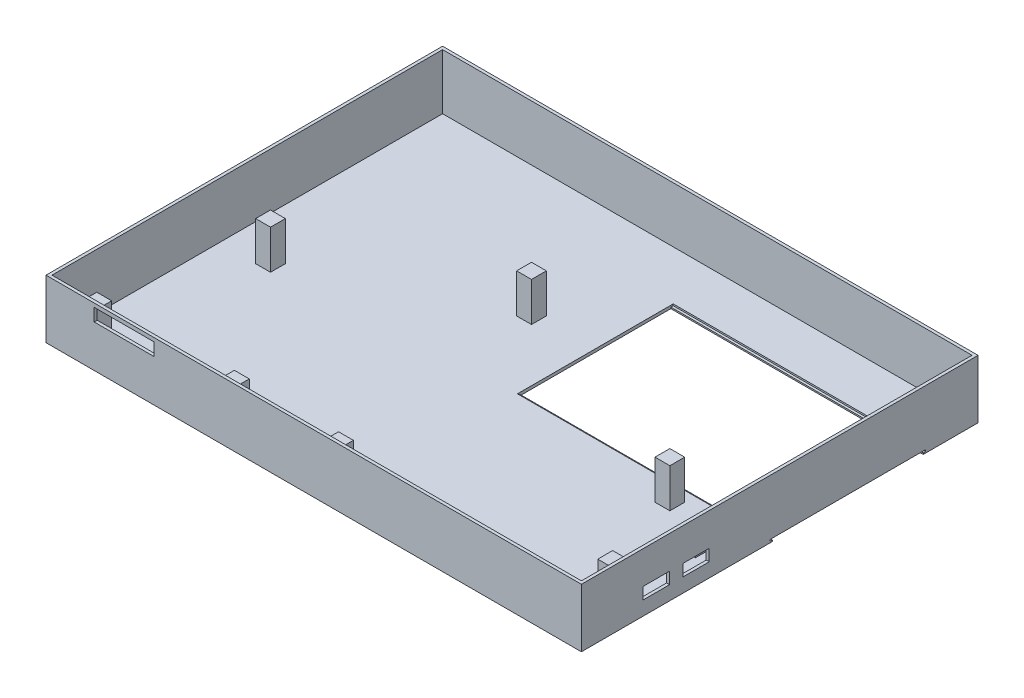
SolidWorks part; units mm, degrees
material "PLA"
ref_plane "Спереди" through (0, 0, 0) normal (0, 0, 1) x (1, 0, 0)
ref_plane "Сверху" through (0, 0, 0) normal (0, 1, 0) x (1, 0, 0)
ref_plane "Справа" through (0, 0, 0) normal (1, 0, 0) x (0, 0, -1)
sketch "Эскиз1" plane through (0, 0, 0) normal (0, 1, 0) x (1, 0, 0)
  line L1 (135, 100) -> (-135, 100)
  line L2 (135, 100) -> (135, -100)
  line L3 (135, -100) -> (-135, -100)
  line L4 (-135, 100) -> (-135, -100)
  line L5 (135, 100) -> (-135, -100) construction
  line L6 (135, -100) -> (-135, 100) construction
  point P0 (0, 0)
  dimension "D1" = 200
  dimension "D2" = 270
extrude "Бобышка-Вытянуть1" add sketch "Эскиз1" along normal blind 1.5
sketch "Эскиз2" plane through (0, 1.5, 0) normal (0, 1, 0) x (1, 0, 0)
  line L0 (133.5, 98.5) -> (-133.5, 98.5)
  line L1 (-133.5, 98.5) -> (-133.5, -98.5)
  line L2 (-133.5, -98.5) -> (-110.7, -98.5)
  line L3 (133.5, -98.5) -> (133.5, 98.5)
  line L4 (-135, 100) -> (-135, -100)
  line L5 (-135, -100) -> (135, -100)
  line L6 (135, -100) -> (135, 100)
  line L7 (135, 100) -> (-135, 100)
  line L8 (-135, 100) -> (-135, -100)
  line L9 (-135, -100) -> (-110.7, -100)
  line L10 (135, -100) -> (135, 100)
  line L11 (135, 100) -> (-135, 100)
  line L12 (-110.7, -98.5) -> (-110.7, -100)
  line L14 (-80.5, -98.5) -> (-80.5, -100)
  line L16 (-80.5, -98.5) -> (133.5, -98.5)
  line L17 (-80.5, -100) -> (135, -100)
  line L18 (-133.5, -98.5) -> (133.5, -98.5) construction
  line L20 (-135, -100) -> (135, -100) construction
  dimension "D3" = 24.3
  dimension "D4" = 54.5
  dimension "D1" = 0
  dimension "D2" = 1.5
extrude "Бобышка-Вытянуть2" add sketch "Эскиз2" along normal offset from surface (28 mm away) 7 offset beyond the face yes
sketch "Эскиз3" plane through (0, 1.5, 0) normal (0, 1, 0) x (1, 0, 0)
  line L1 (-110.7, -98.5) -> (-80.5, -98.5)
  line L2 (-110.7, -98.5) -> (-110.7, -100)
  line L3 (-110.7, -100) -> (-80.5, -100)
  line L4 (-80.5, -98.5) -> (-80.5, -100)
extrude "Бобышка-Вытянуть3" add sketch "Эскиз3" along normal blind 19.7
sketch "Эскиз4" plane through (-110.7, 0, 0) normal (1, 0, 0) x (0, 0, -1)
  line L0 (-100, 29.5) -> (-100, 21.2) construction
  line L1 (-98.5, 29.5) -> (-100, 29.5)
  line L2 (-98.5, 29.5) -> (-98.5, 27.6)
  line L3 (-98.5, 27.6) -> (-100, 27.6)
  line L4 (-100, 29.5) -> (-100, 27.6)
  dimension "D1" = 1.9
extrude "Бобышка-Вытянуть4" add sketch "Эскиз4" along normal up to surface (30.2 mm away) up to face at (-80.5, 25.35, 99.25)
sketch "Эскиз5" plane through (135, 0, 0) normal (1, 0, 0) x (0, 0, -1)
  line L0 (-100, 29.5) -> (-100, 0) construction
  line L1 (-55.55, 13) -> (-68.85, 13)
  line L2 (-55.55, 13) -> (-55.55, 7.1)
  line L3 (-55.55, 7.1) -> (-68.85, 7.1)
  line L4 (-68.85, 13) -> (-68.85, 7.1)
  line L5 (-55.55, 13) -> (-68.85, 7.1) construction
  line L6 (-55.55, 7.1) -> (-68.85, 13) construction
  line L7 (-35.55, 13) -> (-48.85, 13)
  line L8 (-35.55, 13) -> (-35.55, 7.1)
  line L9 (-35.55, 7.1) -> (-48.85, 7.1)
  line L10 (-48.85, 13) -> (-48.85, 7.1)
  line L11 (-35.55, 13) -> (-48.85, 7.1) construction
  line L12 (-35.55, 7.1) -> (-48.85, 13) construction
  line L13 (-100, 0) -> (100, 0) construction
  point P0 (-62.2, 10.05)
  point P5 (-42.2, 10.05)
  dimension "D1" = 13.3
  dimension "D2" = 5.9
  dimension "D3" = 6.7
  dimension "D4" = 31.15
  dimension "D5" = 13
extrude "Вырез-Вытянуть1" cut sketch "Эскиз5" against normal up to surface (1.5 mm away) up to face at (133.5, 15.5, 0)
sketch "Эскиз10" plane through (0, 1.5, 0) normal (0, 1, 0) x (1, 0, 0)
  line L0 (133.5, -14.85) -> (133.5, -98.5) construction
  line L1 (124.175, -24.225) -> (116.675, -24.225)
  line L2 (124.175, -24.225) -> (124.175, -31.725)
  line L3 (124.175, -31.725) -> (116.675, -31.725)
  line L4 (116.675, -24.225) -> (116.675, -31.725)
  line L5 (124.175, -24.225) -> (116.675, -31.725) construction
  line L6 (124.175, -31.725) -> (116.675, -24.225) construction
  line L7 (114.55, -56.3) -> (107.05, -56.3)
  line L8 (114.55, -56.3) -> (114.55, -63.8)
  line L9 (114.55, -63.8) -> (107.05, -63.8)
  line L10 (107.05, -56.3) -> (107.05, -63.8)
  line L11 (114.55, -56.3) -> (107.05, -63.8) construction
  line L12 (114.55, -63.8) -> (107.05, -56.3) construction
  line L13 (115.175, -89.275) -> (107.675, -89.275)
  line L14 (115.175, -89.275) -> (115.175, -96.775)
  line L15 (115.175, -96.775) -> (107.675, -96.775)
  line L16 (107.675, -89.275) -> (107.675, -96.775)
  line L17 (115.175, -89.275) -> (107.675, -96.775) construction
  line L18 (115.175, -96.775) -> (107.675, -89.275) construction
  line L19 (133.5, -98.5) -> (-133.5, -98.5) construction
  point P0 (120.425, -27.975)
  point P5 (110.8, -60.05)
  point P10 (111.425, -93.025)
  dimension "D1" = 13.075
  dimension "D2" = 70.525
  dimension "D3" = 22.7
  dimension "D4" = 38.45
  dimension "D5" = 22.075
  dimension "D6" = 5.475
  dimension "D7" = 7.5
extrude "Бобышка-Вытянуть6" add sketch "Эскиз10" along normal blind 6.9
sketch "Эскиз11" plane through (0, 1.5, 0) normal (0, 1, 0) x (1, 0, 0)
  line L1 (-46.7446, -85.75) -> (-54.2446, -85.75)
  line L2 (-46.7446, -85.75) -> (-46.7446, -93.25)
  line L3 (-46.7446, -93.25) -> (-54.2446, -93.25)
  line L4 (-54.2446, -85.75) -> (-54.2446, -93.25)
  line L5 (-46.7446, -85.75) -> (-54.2446, -93.25) construction
  line L6 (-46.7446, -93.25) -> (-54.2446, -85.75) construction
  line L7 (-19.0224, 28.8491) -> (-26.5224, 28.8491)
  line L8 (-19.0224, 28.8491) -> (-19.0224, 36.3491)
  line L9 (-19.0224, 36.3491) -> (-26.5224, 36.3491)
  line L10 (-26.5224, 28.8491) -> (-26.5224, 36.3491)
  line L11 (-19.0224, 28.8491) -> (-26.5224, 36.3491) construction
  line L12 (-19.0224, 36.3491) -> (-26.5224, 28.8491) construction
  line L13 (-115.5446, -93.8424) -> (-123.0446, -93.8424)
  line L14 (-115.5446, -93.8424) -> (-115.5446, -86.3424)
  line L15 (-115.5446, -86.3424) -> (-123.0446, -86.3424)
  line L16 (-123.0446, -93.8424) -> (-123.0446, -86.3424)
  line L17 (-115.5446, -93.8424) -> (-123.0446, -86.3424) construction
  line L18 (-115.5446, -86.3424) -> (-123.0446, -93.8424) construction
  line L19 (-107.65, -14.1324) -> (-115.15, -14.1324)
  line L20 (-107.65, -14.1324) -> (-107.65, -6.6324)
  line L21 (-107.65, -6.6324) -> (-115.15, -6.6324)
  line L22 (-115.15, -14.1324) -> (-115.15, -6.6324)
  line L23 (-107.65, -14.1324) -> (-115.15, -6.6324) construction
  line L24 (-107.65, -6.6324) -> (-115.15, -14.1324) construction
  line L25 (97.2279, -17.6196) -> (89.7279, -17.6196)
  line L26 (97.2279, -17.6196) -> (97.2279, -10.1196)
  line L27 (97.2279, -10.1196) -> (89.7279, -10.1196)
  line L28 (89.7279, -17.6196) -> (89.7279, -10.1196)
  line L29 (97.2279, -17.6196) -> (89.7279, -10.1196) construction
  line L30 (97.2279, -10.1196) -> (89.7279, -17.6196) construction
  line L31 (94.0554, -99.0196) -> (86.5554, -99.0196)
  line L32 (94.0554, -99.0196) -> (94.0554, -91.5196)
  line L33 (94.0554, -91.5196) -> (86.5554, -91.5196)
  line L34 (86.5554, -99.0196) -> (86.5554, -91.5196)
  line L35 (94.0554, -99.0196) -> (86.5554, -91.5196) construction
  line L36 (94.0554, -91.5196) -> (86.5554, -99.0196) construction
  line L37 (6.3554, -93.8285) -> (-1.1446, -93.8285)
  line L38 (6.3554, -93.8285) -> (6.3554, -86.3285)
  line L39 (6.3554, -86.3285) -> (-1.1446, -86.3285)
  line L40 (-1.1446, -93.8285) -> (-1.1446, -86.3285)
  line L41 (6.3554, -93.8285) -> (-1.1446, -86.3285) construction
  line L42 (6.3554, -86.3285) -> (-1.1446, -93.8285) construction
  line L44 (-133.5, 98.5) -> (133.5, 98.5) construction
  line L45 (-133.5, -98.5) -> (-133.5, 98.5) construction
  line L47 (133.5, -98.5) -> (-133.5, -98.5) construction
  line L48 (133.5, 98.5) -> (133.5, -98.5) construction
  point P0 (-50.4946, -89.5)
  point P5 (-22.7724, 32.5991)
  point P10 (-119.2946, -90.0924)
  point P15 (-111.4, -10.3824)
  point P20 (93.4779, -13.8696)
  point P25 (90.3054, -95.2696)
  point P30 (2.6054, -90.0785)
  dimension "D1" = 7.5
  dimension "D2" = 65.9009
  dimension "D3" = 110.7276
  dimension "D4" = 108.8824
  dimension "D5" = 22.1
  dimension "D6" = 8.4076
  dimension "D7" = 14.2054
  dimension "D8" = 8.4215
  dimension "D9" = 130.8946
  dimension "D10" = 9
  dimension "D11" = 83.0054
  dimension "D12" = 3.2304
  dimension "D13" = 43.1946
  dimension "D14" = 84.6304
  dimension "D15" = 40.0221
extrude "Бобышка-Вытянуть7" add sketch "Эскиз11" along normal blind 19.7
sketch "Эскиз12" plane through (0, 1.5, 0) normal (0, 1, 0) x (1, 0, 0)
  line L1 (135, 72.4) -> (7.7, 72.4)
  line L2 (135, 72.4) -> (135, -3.75)
  line L3 (135, -3.75) -> (7.7, -3.75)
  line L4 (7.7, 72.4) -> (7.7, -3.75)
  line L5 (-133.5, 98.5) -> (133.5, 98.5) construction
  line L6 (135, -100) -> (135, 100) construction
  point P4 (133.5, 84.5609)
  point P5 (135, 70)
  dimension "D1" = 76.15
  dimension "D2" = 127.3
  dimension "D3" = 26.1
extrude "Вырез-Вытянуть2" cut sketch "Эскиз12" against normal through all
sketch "Эскиз13" plane through (135, 0, 0) normal (1, 0, 0) x (0, 0, -1)
  line L0 (34.325, 1.5) -> (34.325, 50001.5) construction
  line L1 (72.4, 1.5) -> (-3.75, 1.5) construction
  line L2 (72.4, 0.7) -> (73.6, 0.7)
  line L3 (-3.75, 1.5) -> (-4.95, 1.5)
  line L4 (-3.75, 1.5) -> (-3.75, 0.7)
  line L5 (-3.75, 0.7) -> (-4.95, 0.7)
  line L6 (-4.95, 1.5) -> (-4.95, 0.7)
  line L7 (73.6, 1.5) -> (73.6, 0.7)
  line L8 (72.4, 1.5) -> (73.6, 1.5)
  line L9 (72.4, 1.5) -> (72.4, 0.7)
  point P4 (34.325, 1.5)
  dimension "D1" = 0.8
  dimension "D2" = 1.2
extrude "Вырез-Вытянуть3" cut sketch "Эскиз13" against normal up to surface (127.3 mm away) up to face at (7.7, 0.75, -34.325)
